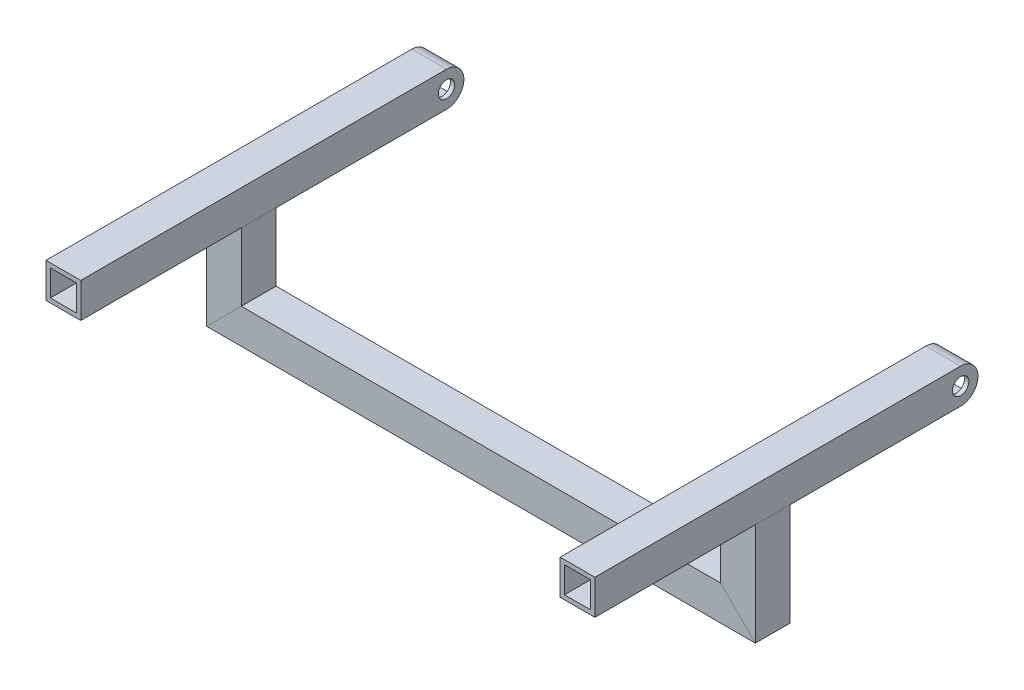
SolidWorks part; units mm, degrees
ref_plane "Front Plane" through (0, 0, 0) normal (0, 0, 1) x (1, 0, 0)
ref_plane "Top Plane" through (0, 0, 0) normal (0, 1, 0) x (1, 0, 0)
ref_plane "Right Plane" through (0, 0, 0) normal (1, 0, 0) x (0, 0, -1)
sketch3d "3DSketch3"
  line L0 (0, 0, 0) -> (0, 0, 280)
  line L1 (375.75, 0, 0) -> (375.75, 0, 280)
  line L6 (0, 0, 150) -> (0, -75, 150)
  line L7 (375.75, 0, 150) -> (375.75, -75, 150)
  line L8 (375.75, -75, 150) -> (0, -75, 150)
  point P5 (0, 0, 150)
  dimension "D1" = 280
  dimension "D2" = 375.75
  dimension "D3" = 150
  dimension "D5" = 75
other "Kickstand Weldments" corner treatment miter
ref_plane "Plane1" through (0, 0, 0) normal (0, 0, 1) x (1, 0, 0)
sketch "Sketch1" plane through (0, 0, 0) normal (0, 0, 1) x (1, 0, 0)
  line L1 (-12.7, 12.7) -> (12.7, 12.7)
  line L2 (-12.7, 12.7) -> (-12.7, -12.7)
  line L3 (-12.7, -12.7) -> (12.7, -12.7)
  line L4 (12.7, 12.7) -> (12.7, -12.7)
  line L5 (-12.7, 12.7) -> (12.7, -12.7) construction
  line L6 (-12.7, -12.7) -> (12.7, 12.7) construction
  line L7 (-9.525, 9.525) -> (9.525, 9.525)
  line L8 (-9.525, 9.525) -> (-9.525, -9.525)
  line L9 (-9.525, -9.525) -> (9.525, -9.525)
  line L10 (9.525, 9.525) -> (9.525, -9.525)
  line L11 (-9.525, 9.525) -> (9.525, -9.525) construction
  line L12 (-9.525, -9.525) -> (9.525, 9.525) construction
  point P0 (0, 0)
  point P6 (0, 0)
  point P11 (0, 0)
  dimension "D1" = 25.4
  dimension "D2" = 3.175
hole_wizard "Ø12.0 (12) Diameter Hole1" positions "Sketch2" profile "Sketch4" hole size "Ø12.0" standard "ANSI Metric"
sketch "Sketch2" plane through (-12.7, 0, 0) normal (-1, 0, 0) x (0, 0, 1)
  line L0 (0, 0) -> (280, 0) construction
  line L1 (0, 12.7) -> (0, -12.7) construction
  point P0 (12.7, 0)
  dimension "D1" = 12.7
sketch "Sketch4" plane through (-12.7, 0, 12.7) normal (0, 1, 0) x (0, 0, 1)
  line L0 (0, 0) -> (0, 29.0052)
  line L1 (0, 29.0052) -> (6, 25.4)
  line L2 (6, 25.4) -> (6, 0)
  line L5 (6, 0) -> (0, 0)
  line L10 (0, 29.0052) -> (-6, 25.4) construction
  line L11 (0, -6.35) -> (0, 107.95) construction
  dimension "Hole Dia." = 12
  dimension "Hole Depth" = 25.4
  dimension "Drill Angle" = 118
ref_plane "Plane2" through (187.875, 0, 0) normal (1, 0, 0) x (0, 0, -1)
mirror "Mirror2" about plane through (187.875, 0, 0) normal (1, 0, 0) of "Ø12.0 (12) Diameter Hole1"
fillet "Fillet1" radius 12.7 2 edges at (0, 12.7, 0) (0, -12.7, 0)
fillet "Fillet2" radius 12.7 2 edges at (375.75, -12.7, 0) (375.75, 12.7, 0)
ref_plane "Plane3" through (375.75, 0, 0) normal (1, 0, 0) x (0, 0, -1)
